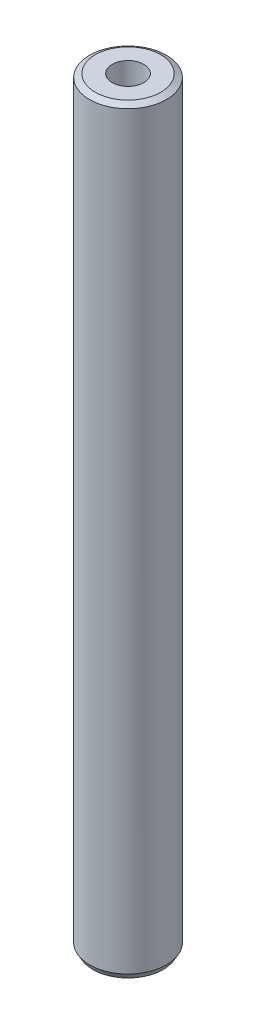
SolidWorks part; units mm, degrees
ref_plane "Front Plane" through (0, 0, 0) normal (0, 0, 1) x (1, 0, 0)
ref_plane "Top Plane" through (0, 0, 0) normal (0, 1, 0) x (1, 0, 0)
ref_plane "Right Plane" through (0, 0, 0) normal (1, 0, 0) x (0, 0, -1)
sketch "Sketch1" plane through (0, 0, 0) normal (0, 1, 0) x (1, 0, 0)
  circle A0 centre (0, 0) radius 25
  dimension "SHAFT_OD" = 50
extrude "Boss-Extrude1" add sketch "Sketch1" along normal blind 493.2088
sketch "Sketch2" plane through (0, 0, 0) normal (0, 1, 0) x (1, 0, 0)
  circle A0 centre (0, 0) radius 10.2938
  dimension "BORE_D" = 20.5876
extrude "Cut-Extrude1" cut sketch "Sketch2" along normal through all
chamfer "Chamfer1" distance 2.1815 angle 60 2 edges at (0, 493.2088, 25) (0, 0, 25) first distance on face at (0, 493.2088, 25) first distance on face at (0, 0, 10.2938)
